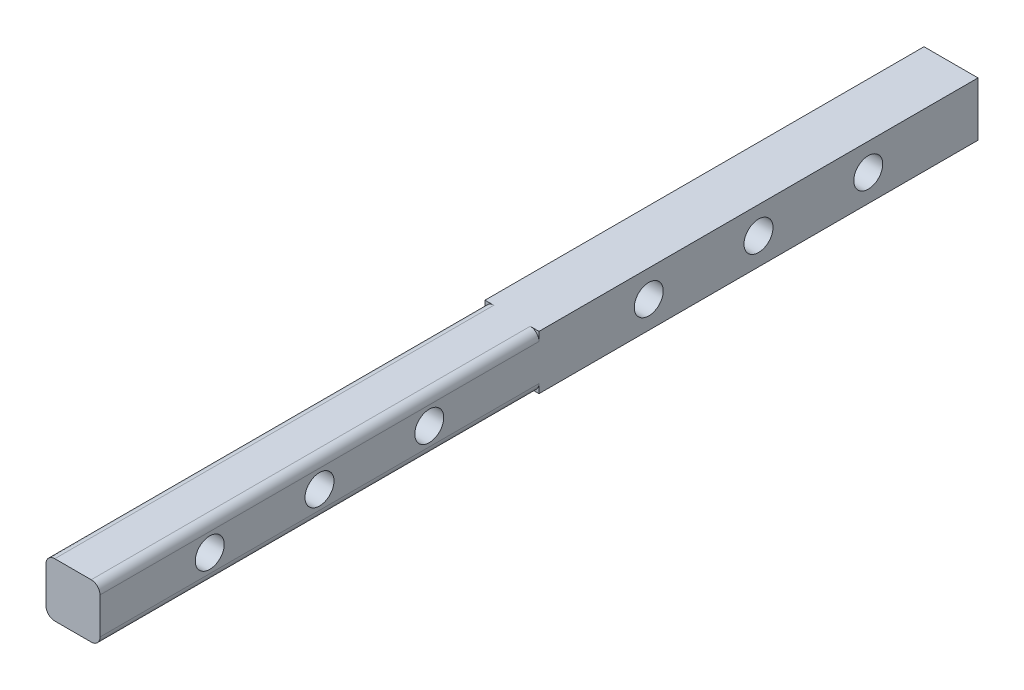
SolidWorks part; units mm, degrees
ref_plane "前视基准面" through (0, 0, 0) normal (0, 0, 1) x (1, 0, 0)
ref_plane "上视基准面" through (0, 0, 0) normal (0, 1, 0) x (1, 0, 0)
ref_plane "右视基准面" through (0, 0, 0) normal (1, 0, 0) x (0, 0, -1)
other "Configuration Table"
sketch "草图1" plane through (0, 0, 0) normal (0, 0, 1) x (1, 0, 0)
  line L1 (-3.075, 3.075) -> (3.075, 3.075)
  line L2 (-3.075, 3.075) -> (-3.075, -3.075)
  line L3 (-3.075, -3.075) -> (3.075, -3.075)
  line L4 (3.075, 3.075) -> (3.075, -3.075)
  line L5 (0, -3.075) -> (0, 3.075) construction
  line L6 (-3.075, 0) -> (3.075, 0) construction
  point P0 (0, 0)
  dimension "D1" = 6.15
  dimension "D2" = 6.15
extrude "凸台-拉伸1" add sketch "草图1" along normal blind 50
fillet "圆角1" radius 1 4 edges at (3.075, -3.075, 25) (-3.075, -3.075, 25) (-3.075, 3.075, 25) (3.075, 3.075, 25)
extrude "凸台-拉伸2" add sketch "草图1<2>" against normal blind 50
sketch "草图1<2>" plane through (0, 0, 0) normal (0, 0, 1) x (1, 0, 0) same geometry as "草图1"
sketch "草图2" plane through (3.075, 0, 0) normal (1, 0, 0) x (0, 0, -1)
  line L0 (-50, 0) -> (50, 0) construction
  line L1 (-50, -2.075) -> (-50, 2.075) construction
  line L2 (50, -3.075) -> (50, 3.075) construction
  line L3 (-37.5, 0) -> (-25, 0) construction
  circle A0 centre (-37.5, 0) radius 1.65
  circle A1 centre (-25, 0) radius 1.65
  circle A2 centre (-12.5, 0) radius 1.65
  circle A3 centre (0, 0) radius 1.65 [skipped]
  circle A4 centre (12.5, 0) radius 1.65
  circle A5 centre (25, 0) radius 1.65
  circle A6 centre (37.5, 0) radius 1.65
  dimension "D1" = 3.3
  dimension "D2" = 12.5
  dimension "D4" = 12.5
  dimension "D3" = 7
extrude "切除-拉伸1" cut sketch "草图2" against normal through all
